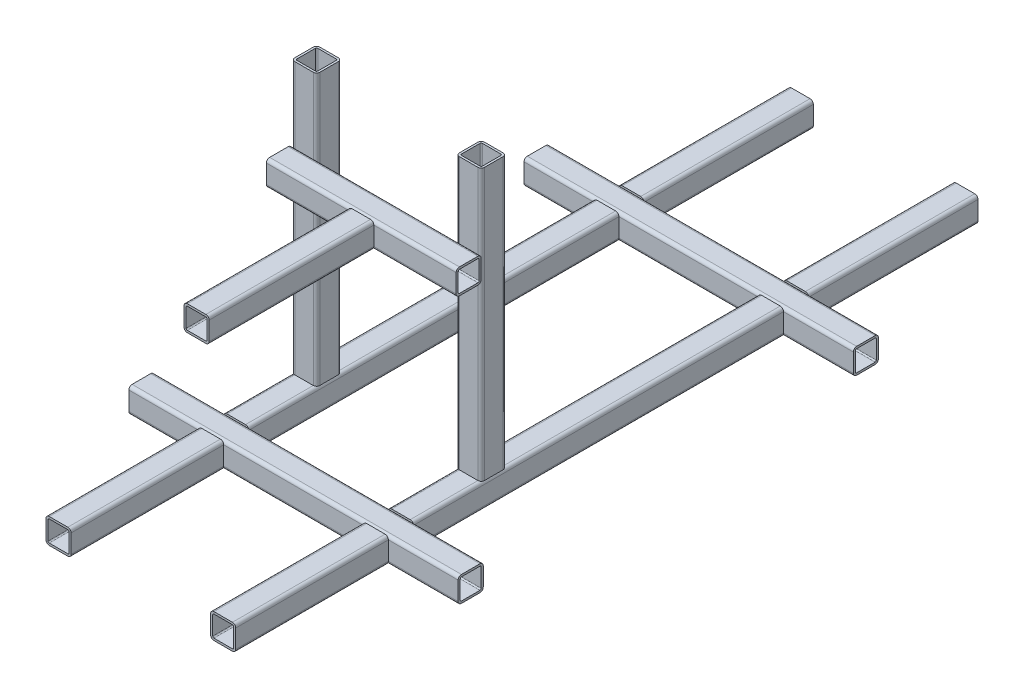
SolidWorks part; units mm, degrees
material "Alumina"
ref_plane "Front Plane" through (0, 0, 0) normal (0, 0, 1) x (1, 0, 0)
ref_plane "Top Plane" through (0, 0, 0) normal (0, 1, 0) x (1, 0, 0)
ref_plane "Right Plane" through (0, 0, 0) normal (1, 0, 0) x (0, 0, -1)
ref_plane "Bottom Face" through (0, 0, 0) normal (0, 1, 0) x (1, 0, 0)
ref_plane "Top Face" through (0, 38.1, 0) normal (0, 1, 0) x (1, 0, 0)
ref_plane "Mid Plane" through (0, 19.05, 0) normal (0, 1, 0) x (1, 0, 0)
ref_plane "Front Face" through (0, 0, 500) normal (0, 0, 1) x (1, 0, 0)
ref_plane "Back Face" through (0, 0, -500) normal (0, 0, 1) x (1, 0, 0)
ref_plane "Left Face" through (250, 0, 0) normal (1, 0, 0) x (0, 0, -1)
ref_plane "Right Face" through (-250, 0, 0) normal (1, 0, 0) x (0, 0, -1)
ref_plane "Divider Plane" through (0, 0, 140) normal (0, 0, 1) x (1, 0, 0)
ref_plane "Max Height Plane" through (0, 450, 0) normal (0, 1, 0) x (1, 0, 0)
ref_plane "Electronics Box Plane" through (0, 338.1, 0) normal (0, 1, 0) x (1, 0, 0)
sketch "Sketch2" plane through (250, 0, 0) normal (1, 0, 0) x (0, 0, -1)
  line L0 (330, 38.1) -> (-330, 38.1) construction
  line L5 (330, 0) -> (-330, 0) construction
  line L6 (0, 220) -> (0, -220) construction
  line L7 (-314.05, 38.1) -> (-285.95, 38.1)
  line L8 (-280.95, 33.1) -> (-280.95, 5)
  line L9 (-315.875, 33.1) -> (-315.875, 5)
  line L10 (-314.05, 3.175) -> (-285.95, 3.175)
  line L11 (-285.95, 0) -> (-314.05, 0)
  line L12 (-319.05, 5) -> (-319.05, 33.1)
  line L13 (-300, 38.1) -> (-300, 0) construction
  line L14 (-319.05, 19.05) -> (-280.95, 19.05) construction
  line L15 (-284.125, 5) -> (-284.125, 33.1)
  line L16 (-285.95, 34.925) -> (-314.05, 34.925)
  line L17 (-300, 34.925) -> (-300, 3.175) construction
  line L18 (-315.875, 19.05) -> (-284.125, 19.05) construction
  arc A0 (-285.95, 38.1) -> (-280.95, 33.1) centre (-285.95, 33.1) cw
  arc A1 (-280.95, 5) -> (-285.95, 0) centre (-285.95, 5) cw
  arc A2 (-314.05, 0) -> (-319.05, 5) centre (-314.05, 5) cw
  arc A3 (-319.05, 33.1) -> (-314.05, 38.1) centre (-314.05, 33.1) cw
  arc A4 (-315.875, 5) -> (-314.05, 3.175) centre (-314.05, 5) ccw
  arc A5 (-285.95, 3.175) -> (-284.125, 5) centre (-285.95, 5) ccw
  arc A6 (-284.125, 33.1) -> (-285.95, 34.925) centre (-285.95, 33.1) ccw
  arc A7 (-314.05, 34.925) -> (-315.875, 33.1) centre (-314.05, 33.1) ccw
  point P20 (-300, 19.05)
  point P39 (-300, 19.05)
  dimension "D1" = 5
  dimension "D2" = 300
  dimension "D3" = 3.175
extrude "Front Cross-Car Member" add sketch "Sketch2" against normal up to surface (500 mm away) up to plane "Right Face"
sketch "Sketch5" plane through (250, 0, 0) normal (1, 0, 0) x (0, 0, -1)
  line L0 (285.95, 38.1) -> (314.05, 38.1)
  line L1 (319.05, 33.1) -> (319.05, 5)
  line L2 (314.05, 0) -> (285.95, 0)
  line L3 (280.95, 5) -> (280.95, 33.1)
  line L4 (300, 38.1) -> (300, 0) construction
  line L5 (280.95, 19.05) -> (319.05, 19.05) construction
  line L6 (285.95, 34.925) -> (314.05, 34.925)
  line L7 (315.875, 33.1) -> (315.875, 5)
  line L8 (314.05, 3.175) -> (285.95, 3.175)
  line L9 (284.125, 5) -> (284.125, 33.1)
  line L10 (300, 34.925) -> (300, 3.175) construction
  line L11 (284.125, 19.05) -> (315.875, 19.05) construction
  line L12 (330, 0) -> (-330, 0) construction
  line L14 (330, 38.1) -> (-330, 38.1) construction
  line L15 (0, 220) -> (0, -220) construction
  arc A0 (314.05, 38.1) -> (319.05, 33.1) centre (314.05, 33.1) cw
  arc A1 (319.05, 5) -> (314.05, 0) centre (314.05, 5) cw
  arc A2 (285.95, 0) -> (280.95, 5) centre (285.95, 5) cw
  arc A3 (280.95, 33.1) -> (285.95, 38.1) centre (285.95, 33.1) cw
  arc A4 (314.05, 34.925) -> (315.875, 33.1) centre (314.05, 33.1) cw
  arc A5 (315.875, 5) -> (314.05, 3.175) centre (314.05, 5) cw
  arc A6 (285.95, 3.175) -> (284.125, 5) centre (285.95, 5) cw
  arc A7 (284.125, 33.1) -> (285.95, 34.925) centre (285.95, 33.1) cw
  point P32 (300, 19.05)
  point P33 (300, 19.05)
  dimension "D2" = 5
  dimension "D1" = 3.175
  dimension "D3" = 300
extrude "Back Cross-Car Member" add sketch "Sketch5" against normal up to surface (500 mm away) separate body up to plane "Right Face"
sketch "Sketch6" plane through (0, 0, -500) normal (0, 0, 1) x (1, 0, 0)
  line L0 (110.95, 38.1) -> (139.05, 38.1)
  line L1 (144.05, 33.1) -> (144.05, 5)
  line L2 (109.125, 33.1) -> (109.125, 5)
  line L3 (110.95, 3.175) -> (139.05, 3.175)
  line L4 (139.05, 0) -> (110.95, 0)
  line L5 (105.95, 5) -> (105.95, 33.1)
  line L6 (125, 38.1) -> (125, 0) construction
  line L7 (105.95, 19.05) -> (144.05, 19.05) construction
  line L8 (140.875, 5) -> (140.875, 33.1)
  line L9 (139.05, 34.925) -> (110.95, 34.925)
  line L10 (125, 34.925) -> (125, 3.175) construction
  line L11 (109.125, 19.05) -> (140.875, 19.05) construction
  line L12 (330, 38.1) -> (-330, 38.1) construction
  line L13 (330, 0) -> (-330, 0) construction
  line L14 (0, -220) -> (0, 220) construction
  arc A0 (139.05, 38.1) -> (144.05, 33.1) centre (139.05, 33.1) cw
  arc A1 (144.05, 5) -> (139.05, 0) centre (139.05, 5) cw
  arc A2 (110.95, 0) -> (105.95, 5) centre (110.95, 5) cw
  arc A3 (105.95, 33.1) -> (110.95, 38.1) centre (110.95, 33.1) cw
  arc A4 (109.125, 5) -> (110.95, 3.175) centre (110.95, 5) ccw
  arc A5 (139.05, 3.175) -> (140.875, 5) centre (139.05, 5) ccw
  arc A6 (140.875, 33.1) -> (139.05, 34.925) centre (139.05, 33.1) ccw
  arc A7 (110.95, 34.925) -> (109.125, 33.1) centre (110.95, 33.1) ccw
  point P16 (125, 19.05)
  point P33 (125, 19.05)
  dimension "D1" = 5
  dimension "D2" = 3.175
  dimension "D3" = 125
extrude "Back Left Along-Car Member" add sketch "Sketch6" along normal blind 180.95 and the other way blind 76.2
extrude "Middle Left Along-Car Member" add sketch "Sketch6<2>" along normal blind 561.9 from offset 219.05
sketch "Sketch6<2>" plane through (0, 0, -500) normal (0, 0, 1) x (1, 0, 0) same geometry as "Sketch6"
extrude "Front Left Along-Car Member" add sketch "Sketch6<3>" along normal blind 231.75 from offset 819.05
sketch "Sketch6<3>" plane through (0, 0, -500) normal (0, 0, 1) x (1, 0, 0) same geometry as "Sketch6"
sketch "Sketch7" plane through (0, 0, -500) normal (0, 0, 1) x (1, 0, 0)
  line L0 (-139.05, 38.1) -> (-110.95, 38.1)
  line L1 (-105.95, 33.1) -> (-105.95, 5)
  line L2 (-140.875, 33.1) -> (-140.875, 5)
  line L3 (-139.05, 3.175) -> (-110.95, 3.175)
  line L4 (-110.95, 0) -> (-139.05, 0)
  line L5 (-144.05, 5) -> (-144.05, 33.1)
  line L6 (-125, 38.1) -> (-125, 0) construction
  line L7 (-144.05, 19.05) -> (-105.95, 19.05) construction
  line L8 (-109.125, 5) -> (-109.125, 33.1)
  line L9 (-110.95, 34.925) -> (-139.05, 34.925)
  line L10 (-125, 34.925) -> (-125, 3.175) construction
  line L11 (-140.875, 19.05) -> (-109.125, 19.05) construction
  line L12 (330, 38.1) -> (-330, 38.1) construction
  line L13 (330, 0) -> (-330, 0) construction
  line L14 (0, -220) -> (0, 220) construction
  arc A0 (-110.95, 38.1) -> (-105.95, 33.1) centre (-110.95, 33.1) cw
  arc A1 (-105.95, 5) -> (-110.95, 0) centre (-110.95, 5) cw
  arc A2 (-139.05, 0) -> (-144.05, 5) centre (-139.05, 5) cw
  arc A3 (-144.05, 33.1) -> (-139.05, 38.1) centre (-139.05, 33.1) cw
  arc A4 (-140.875, 5) -> (-139.05, 3.175) centre (-139.05, 5) ccw
  arc A5 (-110.95, 3.175) -> (-109.125, 5) centre (-110.95, 5) ccw
  arc A6 (-109.125, 33.1) -> (-110.95, 34.925) centre (-110.95, 33.1) ccw
  arc A7 (-139.05, 34.925) -> (-140.875, 33.1) centre (-139.05, 33.1) ccw
  point P16 (-125, 19.05)
  point P33 (-125, 19.05)
  dimension "D1" = 5
  dimension "D2" = 3.175
  dimension "D3" = 125
extrude "Back Right Along-Car Member" add sketch "Sketch7" along normal blind 180.95 and the other way blind 76.2
extrude "Middle Right Along-Car Member" add sketch "Sketch7<2>" along normal blind 561.9 from offset 219.05
sketch "Sketch7<2>" plane through (0, 0, -500) normal (0, 0, 1) x (1, 0, 0) same geometry as "Sketch7"
extrude "Front Right Along-Car Member" add sketch "Sketch7<3>" along normal blind 231.75 from offset 819.05
sketch "Sketch7<3>" plane through (0, 0, -500) normal (0, 0, 1) x (1, 0, 0) same geometry as "Sketch7"
sketch "Sketch8" plane through (0, 38.1, 0) normal (0, 1, 0) x (1, 0, 0)
  line L0 (-139.05, -140) -> (-110.95, -140)
  line L1 (-105.95, -145) -> (-105.95, -173.1)
  line L2 (-140.875, -145) -> (-140.875, -173.1)
  line L3 (-139.05, -174.925) -> (-110.95, -174.925)
  line L4 (-110.95, -178.1) -> (-139.05, -178.1)
  line L5 (-144.05, -173.1) -> (-144.05, -145)
  line L6 (-125, -140) -> (-125, -178.1) construction
  line L7 (-144.05, -159.05) -> (-105.95, -159.05) construction
  line L8 (-109.125, -173.1) -> (-109.125, -145)
  line L9 (-110.95, -143.175) -> (-139.05, -143.175)
  line L10 (-125, -143.175) -> (-125, -174.925) construction
  line L11 (-140.875, -159.05) -> (-109.125, -159.05) construction
  line L12 (-220, -140) -> (220, -140) construction
  line L13 (0, -247.5) -> (0, 247.5) construction
  arc A0 (-110.95, -140) -> (-105.95, -145) centre (-110.95, -145) cw
  arc A1 (-105.95, -173.1) -> (-110.95, -178.1) centre (-110.95, -173.1) cw
  arc A2 (-139.05, -178.1) -> (-144.05, -173.1) centre (-139.05, -173.1) cw
  arc A3 (-144.05, -145) -> (-139.05, -140) centre (-139.05, -145) cw
  arc A4 (-140.875, -173.1) -> (-139.05, -174.925) centre (-139.05, -173.1) ccw
  arc A5 (-110.95, -174.925) -> (-109.125, -173.1) centre (-110.95, -173.1) ccw
  arc A6 (-109.125, -145) -> (-110.95, -143.175) centre (-110.95, -145) ccw
  arc A7 (-139.05, -143.175) -> (-140.875, -145) centre (-139.05, -145) ccw
  point P16 (-125, -159.05)
  point P33 (-125, -159.05)
  dimension "D1" = 5
  dimension "D2" = 3.175
  dimension "D3" = 38.1
  dimension "D4" = 125
extrude "Right Vertical Member" add sketch "Sketch8" along normal up to surface (411.9 mm away) up to plane "Max Height Plane"
sketch "Sketch10" plane through (0, 38.1, 0) normal (0, 1, 0) x (1, 0, 0)
  line L0 (110.95, -140) -> (139.05, -140)
  line L1 (144.05, -145) -> (144.05, -173.1)
  line L2 (109.125, -145) -> (109.125, -173.1)
  line L3 (110.95, -174.925) -> (139.05, -174.925)
  line L4 (139.05, -178.1) -> (110.95, -178.1)
  line L5 (105.95, -173.1) -> (105.95, -145)
  line L6 (125, -140) -> (125, -178.1) construction
  line L7 (105.95, -159.05) -> (144.05, -159.05) construction
  line L8 (140.875, -173.1) -> (140.875, -145)
  line L9 (139.05, -143.175) -> (110.95, -143.175)
  line L10 (125, -143.175) -> (125, -174.925) construction
  line L11 (109.125, -159.05) -> (140.875, -159.05) construction
  line L12 (-220, -140) -> (220, -140) construction
  line L13 (0, -247.5) -> (0, 247.5) construction
  arc A0 (139.05, -140) -> (144.05, -145) centre (139.05, -145) cw
  arc A1 (144.05, -173.1) -> (139.05, -178.1) centre (139.05, -173.1) cw
  arc A2 (110.95, -178.1) -> (105.95, -173.1) centre (110.95, -173.1) cw
  arc A3 (105.95, -145) -> (110.95, -140) centre (110.95, -145) cw
  arc A4 (109.125, -173.1) -> (110.95, -174.925) centre (110.95, -173.1) ccw
  arc A5 (139.05, -174.925) -> (140.875, -173.1) centre (139.05, -173.1) ccw
  arc A6 (140.875, -145) -> (139.05, -143.175) centre (139.05, -145) ccw
  arc A7 (110.95, -143.175) -> (109.125, -145) centre (110.95, -145) ccw
  point P16 (125, -159.05)
  point P33 (125, -159.05)
  dimension "D1" = 5
  dimension "D2" = 3.175
  dimension "D3" = 38.1
  dimension "D4" = 125
extrude "Left Vertical Member" add sketch "Sketch10" along normal up to surface (411.9 mm away) up to plane "Max Height Plane"
sketch "Sketch11" plane through (250, 0, 0) normal (1, 0, 0) x (0, 0, -1)
  line L0 (-211.2, 338.1) -> (-183.1, 338.1)
  line L1 (-178.1, 333.1) -> (-178.1, 305)
  line L2 (-213.025, 333.1) -> (-213.025, 305)
  line L3 (-211.2, 303.175) -> (-183.1, 303.175)
  line L4 (-183.1, 300) -> (-211.2, 300)
  line L5 (-216.2, 305) -> (-216.2, 333.1)
  line L6 (-197.15, 338.1) -> (-197.15, 300) construction
  line L7 (-216.2, 319.05) -> (-178.1, 319.05) construction
  line L8 (-181.275, 305) -> (-181.275, 333.1)
  line L9 (-183.1, 334.925) -> (-211.2, 334.925)
  line L10 (-197.15, 334.925) -> (-197.15, 303.175) construction
  line L11 (-213.025, 319.05) -> (-181.275, 319.05) construction
  line L12 (-140, 220) -> (-140, -220) construction
  line L13 (330, 338.1) -> (-330, 338.1) construction
  arc A0 (-183.1, 338.1) -> (-178.1, 333.1) centre (-183.1, 333.1) cw
  arc A1 (-178.1, 305) -> (-183.1, 300) centre (-183.1, 305) cw
  arc A2 (-211.2, 300) -> (-216.2, 305) centre (-211.2, 305) cw
  arc A3 (-216.2, 333.1) -> (-211.2, 338.1) centre (-211.2, 333.1) cw
  arc A4 (-213.025, 305) -> (-211.2, 303.175) centre (-211.2, 305) ccw
  arc A5 (-183.1, 303.175) -> (-181.275, 305) centre (-183.1, 305) ccw
  arc A6 (-181.275, 333.1) -> (-183.1, 334.925) centre (-183.1, 333.1) ccw
  arc A7 (-211.2, 334.925) -> (-213.025, 333.1) centre (-211.2, 333.1) ccw
  point P16 (-197.15, 319.05)
  point P33 (-197.15, 319.05)
  dimension "D1" = 5
  dimension "D2" = 3.175
  dimension "D3" = 38.1
  dimension "D4" = 38.1
extrude "Upper Cross-Car Member" add sketch "Sketch11" against normal blind 288.1 from offset 105.95 offset against normal yes
sketch "Sketch12" plane through (0, 0, 140) normal (0, 0, 1) x (1, 0, 0)
  line L0 (-14.05, 338.1) -> (14.05, 338.1)
  line L1 (19.05, 333.1) -> (19.05, 305)
  line L2 (-15.875, 333.1) -> (-15.875, 305)
  line L3 (-14.05, 303.175) -> (14.05, 303.175)
  line L4 (14.05, 300) -> (-14.05, 300)
  line L5 (-19.05, 305) -> (-19.05, 333.1)
  line L6 (0, 338.1) -> (0, 300) construction
  line L7 (-19.05, 319.05) -> (19.05, 319.05) construction
  line L8 (15.875, 305) -> (15.875, 333.1)
  line L9 (14.05, 334.925) -> (-14.05, 334.925)
  line L10 (0, 334.925) -> (0, 303.175) construction
  line L11 (-15.875, 319.05) -> (15.875, 319.05) construction
  line L12 (330, 338.1) -> (-330, 338.1) construction
  line L13 (0, -247.5) -> (0, 247.5) construction
  arc A0 (14.05, 338.1) -> (19.05, 333.1) centre (14.05, 333.1) cw
  arc A1 (19.05, 305) -> (14.05, 300) centre (14.05, 305) cw
  arc A2 (-14.05, 300) -> (-19.05, 305) centre (-14.05, 305) cw
  arc A3 (-19.05, 333.1) -> (-14.05, 338.1) centre (-14.05, 333.1) cw
  arc A4 (-15.875, 305) -> (-14.05, 303.175) centre (-14.05, 305) ccw
  arc A5 (14.05, 303.175) -> (15.875, 305) centre (14.05, 305) ccw
  arc A6 (15.875, 333.1) -> (14.05, 334.925) centre (14.05, 333.1) ccw
  arc A7 (-14.05, 334.925) -> (-15.875, 333.1) centre (-14.05, 333.1) ccw
  point P16 (0, 319.05)
  point P33 (0, 319.05)
  dimension "D1" = 5
  dimension "D2" = 3.175
  dimension "D3" = 38.1
extrude "E-Box Platform Base" add sketch "Sketch12" along normal blind 250 from offset 76.2
equation "\"D1@Front Face\" = \"frameLength@Master Assembly.SLDASM\" / 2"
equation "\"D1@Back Face\" = \"frameLength@Master Assembly.SLDASM\" / 2"
equation "\"D1@Left Face\"=\"frameWidth@Master Assembly.SLDASM\"/2"
equation "\"D1@Right Face\" = \"frameWidth@Master Assembly.SLDASM\" / 2"
equation "\"D1@Top Face\"=\"frameTubeStockHeight@Master Assembly.SLDASM\""
equation "\"D2@Sketch2\"=\"frameMemberDistLength@Master Assembly.SLDASM\"/2"
equation "\"D3@Sketch2\"=\"frameTubeStockWallThickness@Master Assembly.SLDASM\""
equation "\"D1@Sketch5\"=\"frameTubeStockWallThickness@Master Assembly.SLDASM\""
equation "\"D3@Sketch5\"=\"frameMemberDistLength@Master Assembly.SLDASM\"/2"
equation "\"D3@Sketch6\"=\"frameMemberDistWidth@Master Assembly.SLDASM\"/2"
equation "\"D1@Back Left Along-Car Member\"=( \"frameLength@Master Assembly.Assembly\" - \"frameMemberDistLength@Master Assembly.Assembly\" - \"frameTubeStockHeight@Master Assembly.Assembly\" )  / 2"
equation "\"D19@Middle Left Along-Car Member\" = ( \"frameLength@Master Assembly.SLDASM\" - \"frameMemberDistLength@Master Assembly.SLDASM\" + \"frameTubeStockHeight@Master Assembly.SLDASM\" ) / 2"
equation "\"D1@Middle Left Along-Car Member\"=\"frameMemberDistLength@Master Assembly.SLDASM\" - \"frameTubeStockHeight@Master Assembly.SLDASM\""
equation "\"D19@Front Left Along-Car Member\"=( \"frameLength@Master Assembly.SLDASM\" - \"frameMemberDistLength@Master Assembly.SLDASM\" )  / 2 + \"frameMemberDistLength@Master Assembly.SLDASM\" + \"frameTubeStockHeight@Master Assembly.SLDASM\" / 2"
equation "\"D1@Front Left Along-Car Member\" =  ( \"frameLength@Master Assembly.Assembly\" - \"frameMemberDistLength@Master Assembly.Assembly\" - \"frameTubeStockHeight@Master Assembly.Assembly\" )  / 2 + 2in"
equation "\"D3@Sketch7\"=\"frameMemberDistWidth@Master Assembly.SLDASM\"/2"
equation "\"D1@Back Right Along-Car Member\"=(\"frameLength@Master Assembly.SLDASM\" - \"frameMemberDistLength@Master Assembly.SLDASM\" - \"frameTubeStockHeight@Master Assembly.SLDASM\")  / 2"
equation "\"D19@Middle Right Along-Car Member\" = ( \"frameLength@Master Assembly.SLDASM\" - \"frameMemberDistLength@Master Assembly.SLDASM\" + \"frameTubeStockHeight@Master Assembly.SLDASM\" ) / 2"
equation "\"D1@Middle Right Along-Car Member\"=\"frameMemberDistLength@Master Assembly.SLDASM\" - \"frameTubeStockHeight@Master Assembly.SLDASM\""
equation "\"D19@Front Right Along-Car Member\"=( \"frameLength@Master Assembly.SLDASM\" - \"frameMemberDistLength@Master Assembly.SLDASM\" )  / 2 + \"frameMemberDistLength@Master Assembly.SLDASM\" + \"frameTubeStockHeight@Master Assembly.SLDASM\" / 2"
equation "\"D1@Front Right Along-Car Member\"=( \"frameLength@Master Assembly.Assembly\" - \"frameMemberDistLength@Master Assembly.Assembly\" - \"frameTubeStockHeight@Master Assembly.Assembly\" )  / 2 + 2in"
equation "\"D1@Divider Plane\"= \"frameDividerPlaneOffset@Master Assembly.SLDASM\""
equation "\"D3@Sketch8\"=\"frameTubeStockHeight@Master Assembly.SLDASM\""
equation "\"D4@Sketch8\"=\"frameMemberDistWidth@Master Assembly.SLDASM\"/2"
equation "\"D1@Max Height Plane\" = \"frameHeight@Master Assembly.SLDASM\""
equation "\"D4@Sketch10\"=\"frameMemberDistWidth@Master Assembly.SLDASM\"/2"
equation "\"D1@Electronics Box Plane\" = \"eboxPlaneHeight@Master Assembly.SLDASM\""
equation "\"D4@Sketch11\"=\"frameTubeStockHeight@Master Assembly.SLDASM\""
equation "\"D19@Upper Cross-Car Member\" = ( \"frameWidth@Master Assembly.SLDASM\" - \"frameMemberDistWidth@Master Assembly.SLDASM\" - \"frameTubeStockHeight@Master Assembly.SLDASM\" ) / 2"
equation "\"D1@Upper Cross-Car Member\" = \"frameMemberDistWidth@Master Assembly.SLDASM\" + \"frameTubeStockHeight@Master Assembly.SLDASM\""
equation "\"D19@E-Box Platform Base\"= \"frameTubeStockHeight@Master Assembly.SLDASM\" * 2"
equation "\"D2@Sketch6\"=\"frameTubeStockWallThickness@Master Assembly.SLDASM\""
equation "\"D2@Sketch7\"=\"frameTubeStockWallThickness@Master Assembly.SLDASM\""
equation "\"D2@Sketch8\"=\"frameTubeStockWallThickness@Master Assembly.SLDASM\""
equation "\"D3@Sketch10\"=\"frameTubeStockHeight@Master Assembly.SLDASM\""
equation "\"D2@Sketch10\"=\"frameTubeStockWallThickness@Master Assembly.SLDASM\""
equation "\"D3@Sketch11\"=\"frameTubeStockHeight@Master Assembly.SLDASM\""
equation "\"D2@Sketch11\"=\"frameTubeStockWallThickness@Master Assembly.SLDASM\""
equation "\"D3@Sketch12\"=\"frameTubeStockHeight@Master Assembly.SLDASM\""
equation "\"D2@Sketch12\"=\"frameTubeStockWallThickness@Master Assembly.SLDASM\""
